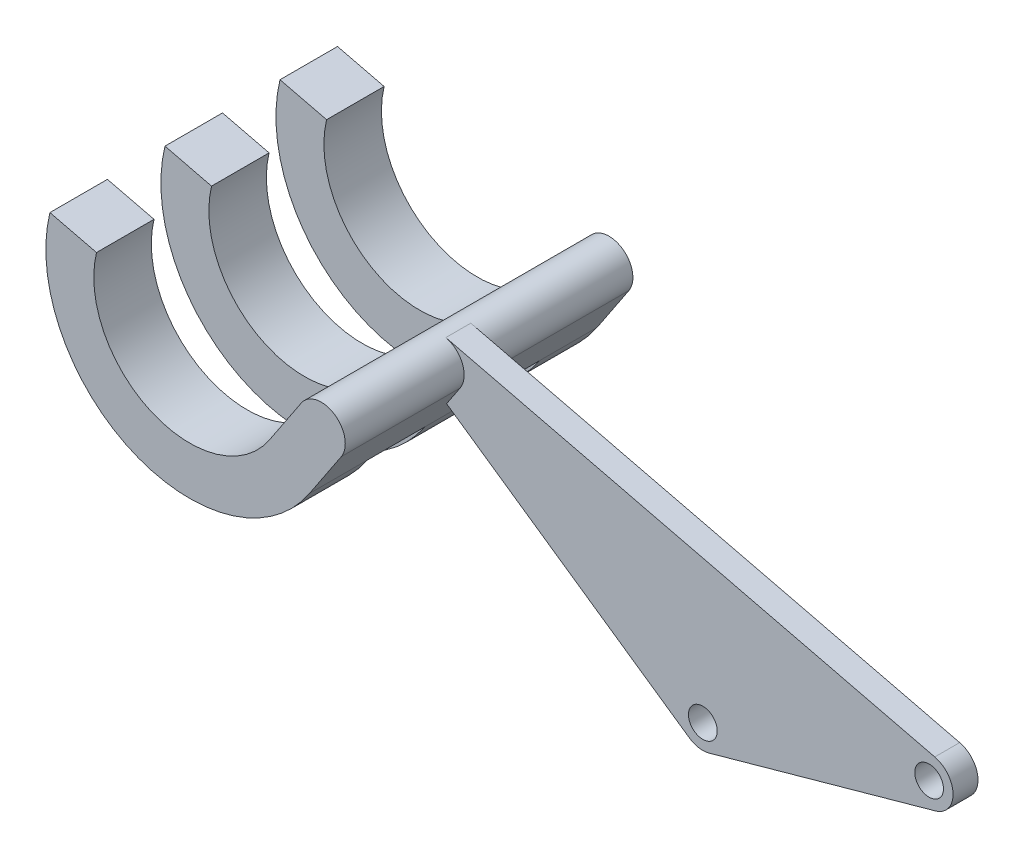
SolidWorks part; units mm, degrees
ref_plane "前基準面" through (0, 0, 0) normal (0, 0, 1) x (1, 0, 0)
ref_plane "上基準面" through (0, 0, 0) normal (0, 1, 0) x (1, 0, 0)
ref_plane "右基準面" through (0, 0, 0) normal (1, 0, 0) x (0, 0, -1)
sketch "草圖1" plane through (0, 0, 0) normal (0, 0, 1) x (1, 0, 0)
  line L0 (10.7414, 6.1934) -> (36.24, 0) construction
  line L1 (36.24, 0) -> (24.4397, -3.2887) construction
  line L2 (24.4397, -3.2887) -> (10.7414, 6.1934) construction
  line L3 (11.0364, 7.4081) -> (36.535, 1.2147)
  line L4 (10.0299, 5.1656) -> (23.7283, -4.3165)
  line L5 (24.7753, -4.4929) -> (36.5756, -1.2041)
  arc A0 (11.0364, 7.4081) -> (10.0299, 5.1656) centre (10.7414, 6.1934) ccw
  arc A1 (36.5756, -1.2041) -> (36.535, 1.2147) centre (36.24, 0) ccw
  arc A2 (23.7283, -4.3165) -> (24.7753, -4.4929) centre (24.4397, -3.2887) ccw
  circle A3 centre (10.7414, 6.1934) radius 0.75
  circle A4 centre (36.24, 0) radius 0.75
  circle A5 centre (24.4397, -3.2887) radius 0.75
  point P12 (24.6333, -6.1643)
  point P14 (4.0291, 0.636)
  point P15 (25.1897, -2.0073)
  point P16 (0, 0)
  point P17 (24.4397, -3.2887)
  point P19 (36.24, 0.75)
  point P20 (36.24, 0)
  point P21 (0, 0)
  point P22 (0.4425, 2.3903)
  point P23 (36.9088, 0.3395)
  point P26 (0, 0)
  point P27 (0, 0)
  dimension "D3" = 2.5
  dimension "D5" = 1.5
  dimension "D2" = 16.66
  dimension "D4" = 26.24
extrude "填料-伸長1" add sketch "草圖1" along normal mid plane 1.3
sketch "草圖2" plane through (0, 0, -0.65) normal (0, 0, -1) x (-1, 0, 0)
  line L0 (-11.7819, 5.5007) -> (-10.1195, 3.0035)
  line L1 (-9.7009, 6.8861) -> (-8.0384, 4.3889)
  line L2 (0.9824, 8.3398) -> (0.7717, 9.2071) construction
  line L3 (0.9824, 8.3398) -> (3.4118, 8.9298)
  line L4 (-36.535, 1.2147) -> (-11.0364, 7.4081) construction
  arc A0 (-9.7009, 6.8861) -> (-11.7819, 5.5007) centre (-10.7414, 6.1934) ccw
  arc A1 (-8.0384, 4.3889) -> (0.9824, 8.3398) centre (-3.8763, 7.1596) ccw
  arc A2 (-10.1195, 3.0035) -> (3.4118, 8.9298) centre (-3.8763, 7.1596) ccw
  arc A7 (-10.0299, 5.1656) -> (-11.0364, 7.4081) centre (-10.7414, 6.1934) ccw construction
  dimension "D1" = 5
  dimension "D2" = 20
  dimension "D3" = 250
  dimension "D4" = 3
extrude "填料-伸長2" add sketch "草圖2" along normal mid plane 15 contours A2 L3 A1 L1 A0 L0
sketch "草圖3" plane through (0, 0, 0.85) normal (0, 0, -1) x (-1, 0, 0)
  line L2 (0.9824, 8.3398) -> (3.4118, 8.9298) construction
  line L10 (-10.1195, 3.0035) -> (-8.0384, 4.3889)
  line L13 (0.9824, 8.3398) -> (3.4118, 8.9298)
  arc A1 (-8.0384, 4.3889) -> (0.9824, 8.3398) centre (-3.8763, 7.1596) ccw construction
  arc A2 (-10.1195, 3.0035) -> (3.4118, 8.9298) centre (-3.8763, 7.1596) ccw construction
  arc A10 (-8.0384, 4.3889) -> (0.9824, 8.3398) centre (-3.8763, 7.1596) ccw
  arc A11 (-10.1195, 3.0035) -> (3.4118, 8.9298) centre (-3.8763, 7.1596) ccw
extrude "除料-伸長2" cut sketch "草圖3" against normal blind 3
ref_plane "平面2" through (0, 0, -2.15) normal (0, 0, 1) x (1, 0, 0)
sketch "草圖5" plane through (0, 0, -2.15) normal (0, 0, 1) x (1, 0, 0)
  line L0 (8.0384, 4.3889) -> (10.1195, 3.0035) construction
  line L1 (-0.9824, 8.3398) -> (-3.4118, 8.9298) construction
  line L2 (8.0384, 4.3889) -> (10.1195, 3.0035)
  line L3 (-0.9824, 8.3398) -> (-3.4118, 8.9298)
  arc A0 (-3.4118, 8.9298) -> (10.1195, 3.0035) centre (3.8763, 7.1596) ccw construction
  arc A1 (-0.9824, 8.3398) -> (8.0384, 4.3889) centre (3.8763, 7.1596) ccw construction
  arc A2 (-3.4118, 8.9298) -> (10.1195, 3.0035) centre (3.8763, 7.1596) ccw
  arc A3 (-0.9824, 8.3398) -> (8.0384, 4.3889) centre (3.8763, 7.1596) ccw
extrude "除料-伸長3" cut sketch "草圖5" against normal blind 3
